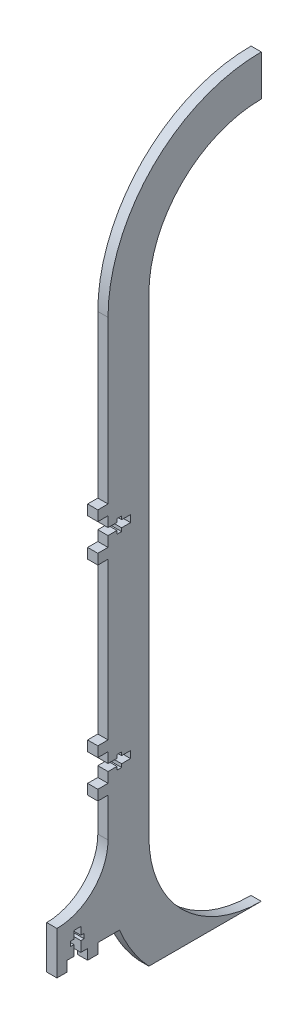
SolidWorks part; units mm, degrees
ref_plane "Front Plane" through (0, 0, 0) normal (0, 0, 1) x (1, 0, 0)
ref_plane "Top Plane" through (0, 0, 0) normal (0, 1, 0) x (1, 0, 0)
ref_plane "Right Plane" through (0, 0, 0) normal (1, 0, 0) x (0, 0, -1)
sketch "Elevator Ball Support Rail" plane through (0, 0, 0) normal (1, 0, 0) x (0, 0, -1)
  line L0 (69.85, 215.9) -> (69.85, 241.3)
  line L1 (-31.75, -111.125) -> (-25.4, -111.125)
  line L2 (69.85, -215.9) -> (0, -215.9)
  line L3 (-31.75, -187.325) -> (-18.2601, -187.325)
  line L4 (-38.1, -193.675) -> (-31.75, -193.675)
  line L5 (-38.1, -187.325) -> (-38.1, -193.675)
  line L6 (0, 146.05) -> (0, -146.05)
  line L7 (-25.4, -135.255) -> (-25.4, -187.325) construction
  line L8 (0, -146.05) -> (0, -215.9) construction
  line L9 (-31.75, -187.325) -> (-31.75, -193.675)
  line L10 (-50.8, -187.325) -> (-46.609, -187.325)
  line L11 (-25.4, 39.243) -> (-25.4, 32.893)
  line L12 (-57.15, -167.005) -> (-57.15, -193.675)
  line L13 (-57.15, -193.675) -> (-50.8, -193.675)
  line L14 (-42.291, -187.325) -> (-38.1, -187.325)
  line L15 (-50.8, -193.675) -> (-50.8, -187.325)
  line L16 (-42.291, -180.975) -> (-42.291, -187.325)
  line L17 (-42.291, -180.975) -> (-40.25, -180.975)
  line L18 (-40.25, -180.975) -> (-40.25, -178.075)
  line L19 (-42.291, -178.075) -> (-42.291, -173.355)
  line L20 (-42.291, -173.355) -> (-46.609, -173.355)
  line L21 (-40.25, -178.075) -> (-42.291, -178.075)
  line L22 (-48.65, -178.075) -> (-48.65, -180.975)
  line L23 (-48.65, -180.975) -> (-46.609, -180.975)
  line L24 (-46.609, -180.975) -> (-46.609, -187.325)
  line L25 (-46.609, -173.355) -> (-46.609, -178.075)
  line L26 (-46.609, -178.075) -> (-48.65, -178.075)
  line L27 (0, -187.325) -> (101.6, -187.325) construction
  line L28 (-31.75, 45.593) -> (-31.75, 39.243)
  line L29 (-31.75, 39.243) -> (-25.4, 39.243)
  line L30 (-25.4, 32.893) -> (-19.865, 32.893)
  line L31 (-19.865, 32.893) -> (-19.865, 34.934)
  line L32 (-19.865, 34.934) -> (-16.965, 34.934)
  line L33 (-16.965, 34.934) -> (-16.965, 32.893)
  line L34 (-16.965, 32.893) -> (-11.43, 32.893)
  line L35 (-11.43, 32.893) -> (-11.43, 28.575)
  line L36 (-11.43, 28.575) -> (-16.965, 28.575)
  line L37 (-16.965, 28.575) -> (-16.965, 26.534)
  line L38 (-16.965, 26.534) -> (-19.865, 26.534)
  line L39 (-19.865, 26.534) -> (-19.865, 28.575)
  line L40 (-19.865, 28.575) -> (-25.4, 28.575)
  line L41 (-25.4, 28.575) -> (-25.4, 22.225)
  line L42 (0, 0) -> (-25.4, 0) construction
  line L43 (-25.4, 22.225) -> (-31.75, 22.225)
  line L44 (-31.75, 22.225) -> (-31.75, 15.875)
  line L45 (-31.75, 15.875) -> (-25.4, 15.875)
  line L46 (-25.4, 15.875) -> (-25.4, -81.407)
  line L47 (-25.4, -81.407) -> (-31.75, -81.407)
  line L48 (-25.4, -87.757) -> (-25.4, -94.107)
  line L49 (-31.75, -81.407) -> (-31.75, -87.757)
  line L50 (-31.75, -87.757) -> (-25.4, -87.757)
  line L51 (-25.4, -94.107) -> (-19.865, -94.107)
  line L52 (-19.865, -94.107) -> (-19.865, -92.066)
  line L53 (-19.865, -92.066) -> (-16.965, -92.066)
  line L54 (-16.965, -92.066) -> (-16.965, -94.107)
  line L55 (-16.965, -94.107) -> (-11.43, -94.107)
  line L56 (-11.43, -94.107) -> (-11.43, -98.425)
  line L57 (-11.43, -98.425) -> (-16.965, -98.425)
  line L58 (-16.965, -98.425) -> (-16.965, -100.466)
  line L59 (-16.965, -100.466) -> (-19.865, -100.466)
  line L60 (-19.865, -100.466) -> (-19.865, -98.425)
  line L61 (-19.865, -98.425) -> (-25.4, -98.425)
  line L62 (-25.4, -98.425) -> (-25.4, -104.775)
  line L63 (-25.4, -104.775) -> (-31.75, -104.775)
  line L64 (-31.75, -104.775) -> (-31.75, -111.125)
  line L65 (-25.4, -135.255) -> (-25.4, -128.905)
  line L66 (-25.4, -111.125) -> (-25.4, -128.905)
  line L67 (-31.75, 45.593) -> (-25.4, 45.593)
  line L68 (-25.4, 45.593) -> (-25.4, 146.05)
  arc A0 (0, 146.05) -> (69.85, 215.9) centre (69.85, 146.05) cw
  arc A1 (69.85, 241.3) -> (-25.4, 146.05) centre (69.85, 146.05) ccw
  arc A2 (0, -146.05) -> (69.85, -215.9) centre (69.85, -146.05) ccw
  arc A3 (-18.2601, -187.325) -> (0, -215.9) centre (69.85, -151.1425) ccw
  arc A4 (-57.15, -167.005) -> (-25.4, -135.255) centre (-57.15, -135.255) ccw
  point P4 (0, 0)
  dimension "D5" = 25.4
  dimension "D4" = 69.85
  dimension "D7" = 69.85
  dimension "D8" = 6.35
  dimension "D14" = 12.7
  dimension "D13" = 6.35
  dimension "D6" = 6.35
  dimension "D3" = 292.1
  dimension "D9" = 22.225
  dimension "D10" = 6.35
  dimension "D11" = 6.35
  dimension "D12" = 6.35
  dimension "D15" = 2.9
  dimension "D16" = 8.4
  dimension "D17" = 6.35
  dimension "D18" = 4.318
  dimension "D19" = 13.97
  dimension "D20" = 41.275
  dimension "D21" = 6.35
  dimension "D22" = 6.35
  dimension "D23" = 4.318
  dimension "D24" = 2.9
  dimension "D25" = 8.4
  dimension "D26" = 6.35
  dimension "D27" = 13.97
  dimension "D28" = 6.35
  dimension "D29" = 4.318
  dimension "D30" = 2.9
  dimension "D31" = 13.97
  dimension "D32" = 6.35
  dimension "D33" = 8.4
  dimension "D34" = 6.35
  dimension "D35" = 6.35
  dimension "D36" = 25.4
  dimension "D37" = 76.2
  dimension "D38" = 203.2
extrude "Boss-Extrude2" add sketch "Elevator Ball Support Rail" along normal blind 6.35
equation "\"Ball Diameter\"= 1.75in"
equation "\"Pulley Diameter\" = 1in"
equation "\"Reactor Height\" = 14in"
equation "\"Sheet Thickness\"= 0.25in"
equation "\"Screw Diameter\"= .17in"
equation "\"Robot Diameter\"= 14in"
equation "\"Castor Screw Diameter\"= 0.22in"
equation "\"Wheel Diameter\" = 4in"
equation "\"Nut Diameter\" = 8.4mm"
equation "\"Nut Height\" = 2.9mm"
equation "\"Screw Height\" = 0.55in"
equation "\"D11@Elevator Ball Support Rail\"=\"Sheet Thickness\""
equation "\"Elevator Height\" = 11.5in"
equation "\"D12@Elevator Ball Support Rail\"=\"Sheet Thickness\""
equation "\"D7@Elevator Ball Support Rail\"=\"Elevator Clearance from Axis\""
equation "\"D10@Elevator Ball Support Rail\"=\"Sheet Thickness\""
equation "\"D13@Elevator Ball Support Rail\"=\"Sheet Thickness\""
equation "\"D1@T-Slot\" = \"Screw Diameter\""
equation "\"D16@Elevator Ball Support Rail\"=\"Nut Diameter\""
equation "\"D15@Elevator Ball Support Rail\"=\"Nut Height\""
equation "\"D16@Elevator Ball Support Rail\" = \"Nut Diameter\""
equation "\"D9@Elevator Ball Support Rail\"=\"Ball Diameter\"/2"
equation "\"D1@Boss-Extrude2\"=\"Sheet Thickness\""
equation "\"D18@Elevator Ball Support Rail\"=\"Screw Diameter\""
equation "\"D19@Elevator Ball Support Rail\"=\"Screw Height\""
equation "\"D3@Elevator Ball Support Rail\"=\"Elevator Height\""
equation "\"Elevator Width\" = \"Ball Diameter\" + 0.25in"
equation "\"Elevator Bearing Diameter\" = sqr(2*(\"Sheet Thickness\"^2)) + 0.2in"
equation "\"Elevator Axle Endcap Diameter\" = \"Pulley Diameter\" + 0.25in"
equation "\"Elevator Axle Length\" = \"Elevator Width\" + 8*\"Sheet Thickness\""
equation "\"Elevator Clearance from Axis\" = (\"Pulley Diameter\"/2) + \"Ball Diameter\" + 0.5in"
equation "\"D4@Elevator Ball Support Rail\"=\"Elevator Clearance from Axis\""
equation "\"D21@Elevator Ball Support Rail\"=\"Sheet Thickness\""
equation "\"D22@Elevator Ball Support Rail\"=\"Sheet Thickness\""
equation "\"D23@Elevator Ball Support Rail\"=\"Screw Diameter\""
equation "\"D24@Elevator Ball Support Rail\"=\"Nut Height\""
equation "\"D25@Elevator Ball Support Rail\"=\"Nut Diameter\""
equation "\"D26@Elevator Ball Support Rail\"=\"Sheet Thickness\""
equation "\"D27@Elevator Ball Support Rail\"=\"Screw Height\""
equation "\"D32@Elevator Ball Support Rail\"=\"Sheet Thickness\""
equation "\"D33@Elevator Ball Support Rail\"=\"Nut Diameter\""
equation "\"D34@Elevator Ball Support Rail\"=\"Sheet Thickness\""
equation "\"D35@Elevator Ball Support Rail\"=\"Sheet Thickness\""
equation "\"D30@Elevator Ball Support Rail\"=\"Nut Height\""
equation "\"D28@Elevator Ball Support Rail\"=\"Sheet Thickness\""
equation "\"D29@Elevator Ball Support Rail\"=\"Screw Diameter\""
equation "\"D31@Elevator Ball Support Rail\"=\"Screw Height\""
